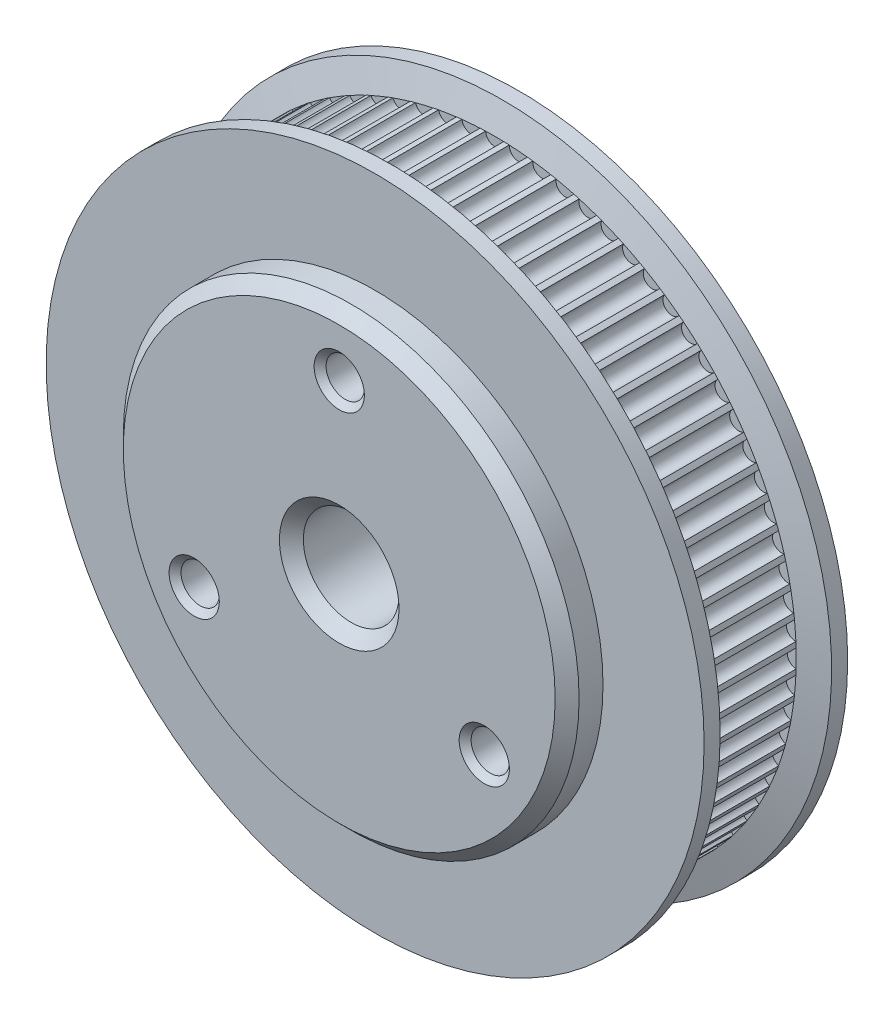
SolidWorks part; units mm, degrees
material "ABS"
ref_plane "Plan de face" through (0, 0, 0) normal (0, 0, 1) x (1, 0, 0)
ref_plane "Plan de dessus" through (0, 0, 0) normal (0, 1, 0) x (1, 0, 0)
ref_plane "Plan de droite" through (0, 0, 0) normal (1, 0, 0) x (0, 0, -1)
sketch "Esquisse1" plane through (0, 0, 0) normal (0, 0, 1) x (1, 0, 0)
  line L0 (0, 0) -> (0, 25.2095) construction
  arc A0 (0.7599, -25.198) -> (1.2194, -25.18) centre (0, 0) ccw
  arc A1 (-0.7599, 25.198) -> (0.7599, 25.198) centre (0, 25.2095) ccw
  arc A2 (-6.6213, 24.3244) -> (-7.0639, 24.1996) centre (0, 0) ccw
  arc A3 (1.2194, 25.18) -> (2.7346, 25.0607) centre (1.9779, 25.1318) ccw
  arc A4 (3.1913, 25.0067) -> (4.6924, 24.7689) centre (3.9436, 24.8991) ccw
  arc A5 (5.1434, 24.6792) -> (6.6213, 24.3244) centre (5.885, 24.513) ccw
  arc A6 (7.0639, 24.1996) -> (8.5093, 23.7299) centre (7.7902, 23.9757) ccw
  arc A7 (8.9408, 23.5708) -> (10.3449, 22.9892) centre (9.6473, 23.2905) ccw
  arc A8 (10.7626, 22.7966) -> (12.1168, 22.1066) centre (11.4449, 22.4618) ccw
  arc A9 (12.518, 21.8819) -> (13.8139, 21.0878) centre (13.1719, 21.4946) ccw
  arc A10 (14.1963, 20.8323) -> (15.4258, 19.939) centre (14.8178, 20.3949) ccw
  arc A11 (15.787, 19.6543) -> (16.9427, 18.6672) centre (16.3723, 19.1695) ccw
  arc A12 (17.2804, 18.355) -> (18.355, 17.2804) centre (17.8258, 17.8258) ccw
  arc A13 (18.6672, 16.9427) -> (19.6543, 15.787) centre (19.1695, 16.3723) ccw
  arc A14 (19.939, 15.4258) -> (20.8323, 14.1963) centre (20.3949, 14.8178) ccw
  arc A15 (21.0878, 13.8139) -> (21.8819, 12.518) centre (21.4946, 13.1719) ccw
  arc A16 (22.1066, 12.1168) -> (22.7966, 10.7626) centre (22.4618, 11.4449) ccw
  arc A17 (22.9892, 10.3449) -> (23.5708, 8.9408) centre (23.2905, 9.6473) ccw
  arc A18 (23.7299, 8.5093) -> (24.1996, 7.0639) centre (23.9757, 7.7902) ccw
  arc A19 (24.3244, 6.6213) -> (24.6792, 5.1434) centre (24.513, 5.885) ccw
  arc A20 (24.7689, 4.6924) -> (25.0067, 3.1913) centre (24.8991, 3.9436) ccw
  arc A21 (25.0607, 2.7346) -> (25.18, 1.2194) centre (25.1318, 1.9779) ccw
  arc A22 (25.198, 0.7599) -> (25.198, -0.7599) centre (25.2095, 0) ccw
  arc A23 (25.18, -1.2194) -> (25.0607, -2.7346) centre (25.1318, -1.9779) ccw
  arc A24 (25.0067, -3.1913) -> (24.7689, -4.6924) centre (24.8991, -3.9436) ccw
  arc A25 (24.6792, -5.1434) -> (24.3244, -6.6213) centre (24.513, -5.885) ccw
  arc A26 (24.1996, -7.0639) -> (23.7299, -8.5093) centre (23.9757, -7.7902) ccw
  arc A27 (23.5708, -8.9408) -> (22.9892, -10.3449) centre (23.2905, -9.6473) ccw
  arc A28 (22.7966, -10.7626) -> (22.1066, -12.1168) centre (22.4618, -11.4449) ccw
  arc A29 (21.8819, -12.518) -> (21.0878, -13.8139) centre (21.4946, -13.1719) ccw
  arc A30 (20.8323, -14.1963) -> (19.939, -15.4258) centre (20.3949, -14.8178) ccw
  arc A31 (19.6543, -15.787) -> (18.6672, -16.9427) centre (19.1695, -16.3723) ccw
  arc A32 (18.355, -17.2804) -> (17.2804, -18.355) centre (17.8258, -17.8258) ccw
  arc A33 (16.9427, -18.6672) -> (15.787, -19.6543) centre (16.3723, -19.1695) ccw
  arc A34 (15.4258, -19.939) -> (14.1963, -20.8323) centre (14.8178, -20.3949) ccw
  arc A35 (13.8139, -21.0878) -> (12.518, -21.8819) centre (13.1719, -21.4946) ccw
  arc A36 (12.1168, -22.1066) -> (10.7626, -22.7966) centre (11.4449, -22.4618) ccw
  arc A37 (10.3449, -22.9892) -> (8.9408, -23.5708) centre (9.6473, -23.2905) ccw
  arc A38 (8.5093, -23.7299) -> (7.0639, -24.1996) centre (7.7902, -23.9757) ccw
  arc A39 (6.6213, -24.3244) -> (5.1434, -24.6792) centre (5.885, -24.513) ccw
  arc A40 (4.6924, -24.7689) -> (3.1913, -25.0067) centre (3.9436, -24.8991) ccw
  arc A41 (2.7346, -25.0607) -> (1.2194, -25.18) centre (1.9779, -25.1318) ccw
  arc A42 (0.7599, -25.198) -> (-0.7599, -25.198) centre (0, -25.2095) ccw
  arc A43 (-1.2194, -25.18) -> (-2.7346, -25.0607) centre (-1.9779, -25.1318) ccw
  arc A44 (-3.1913, -25.0067) -> (-4.6924, -24.7689) centre (-3.9436, -24.8991) ccw
  arc A45 (-5.1434, -24.6792) -> (-6.6213, -24.3244) centre (-5.885, -24.513) ccw
  arc A46 (-7.0639, -24.1996) -> (-8.5093, -23.7299) centre (-7.7902, -23.9757) ccw
  arc A47 (-8.9408, -23.5708) -> (-10.3449, -22.9892) centre (-9.6473, -23.2905) ccw
  arc A48 (-10.7626, -22.7966) -> (-12.1168, -22.1066) centre (-11.4449, -22.4618) ccw
  arc A49 (-12.518, -21.8819) -> (-13.8139, -21.0878) centre (-13.1719, -21.4946) ccw
  arc A50 (-14.1963, -20.8323) -> (-15.4258, -19.939) centre (-14.8178, -20.3949) ccw
  arc A51 (-15.787, -19.6543) -> (-16.9427, -18.6672) centre (-16.3723, -19.1695) ccw
  arc A52 (-17.2804, -18.355) -> (-18.355, -17.2804) centre (-17.8258, -17.8258) ccw
  arc A53 (-18.6672, -16.9427) -> (-19.6543, -15.787) centre (-19.1695, -16.3723) ccw
  arc A54 (-19.939, -15.4258) -> (-20.8323, -14.1963) centre (-20.3949, -14.8178) ccw
  arc A55 (-21.0878, -13.8139) -> (-21.8819, -12.518) centre (-21.4946, -13.1719) ccw
  arc A56 (-22.1066, -12.1168) -> (-22.7966, -10.7626) centre (-22.4618, -11.4449) ccw
  arc A57 (-22.9892, -10.3449) -> (-23.5708, -8.9408) centre (-23.2905, -9.6473) ccw
  arc A58 (-23.7299, -8.5093) -> (-24.1996, -7.0639) centre (-23.9757, -7.7902) ccw
  arc A59 (-24.3244, -6.6213) -> (-24.6792, -5.1434) centre (-24.513, -5.885) ccw
  arc A60 (-24.7689, -4.6924) -> (-25.0067, -3.1913) centre (-24.8991, -3.9436) ccw
  arc A61 (-25.0607, -2.7346) -> (-25.18, -1.2194) centre (-25.1318, -1.9779) ccw
  arc A62 (-25.198, -0.7599) -> (-25.198, 0.7599) centre (-25.2095, 0) ccw
  arc A63 (-25.18, 1.2194) -> (-25.0607, 2.7346) centre (-25.1318, 1.9779) ccw
  arc A64 (-25.0067, 3.1913) -> (-24.7689, 4.6924) centre (-24.8991, 3.9436) ccw
  arc A65 (-24.6792, 5.1434) -> (-24.3244, 6.6213) centre (-24.513, 5.885) ccw
  arc A66 (-24.1996, 7.0639) -> (-23.7299, 8.5093) centre (-23.9757, 7.7902) ccw
  arc A67 (-23.5708, 8.9408) -> (-22.9892, 10.3449) centre (-23.2905, 9.6473) ccw
  arc A68 (-22.7966, 10.7626) -> (-22.1066, 12.1168) centre (-22.4618, 11.4449) ccw
  arc A69 (-21.8819, 12.518) -> (-21.0878, 13.8139) centre (-21.4946, 13.1719) ccw
  arc A70 (-20.8323, 14.1963) -> (-19.939, 15.4258) centre (-20.3949, 14.8178) ccw
  arc A71 (-19.6543, 15.787) -> (-18.6672, 16.9427) centre (-19.1695, 16.3723) ccw
  arc A72 (-18.355, 17.2804) -> (-17.2804, 18.355) centre (-17.8258, 17.8258) ccw
  arc A73 (-16.9427, 18.6672) -> (-15.787, 19.6543) centre (-16.3723, 19.1695) ccw
  arc A74 (-15.4258, 19.939) -> (-14.1963, 20.8323) centre (-14.8178, 20.3949) ccw
  arc A75 (-13.8139, 21.0878) -> (-12.518, 21.8819) centre (-13.1719, 21.4946) ccw
  arc A76 (-12.1168, 22.1066) -> (-10.7626, 22.7966) centre (-11.4449, 22.4618) ccw
  arc A77 (-10.3449, 22.9892) -> (-8.9408, 23.5708) centre (-9.6473, 23.2905) ccw
  arc A78 (-8.5093, 23.7299) -> (-7.0639, 24.1996) centre (-7.7902, 23.9757) ccw
  arc A79 (-6.6213, 24.3244) -> (-5.1434, 24.6792) centre (-5.885, 24.513) ccw
  arc A80 (-4.6924, 24.7689) -> (-3.1913, 25.0067) centre (-3.9436, 24.8991) ccw
  arc A81 (-2.7346, 25.0607) -> (-1.2194, 25.18) centre (-1.9779, 25.1318) ccw
  arc A82 (-8.5093, 23.7299) -> (-8.9408, 23.5708) centre (0, 0) ccw
  arc A83 (-10.3449, 22.9892) -> (-10.7626, 22.7966) centre (0, 0) ccw
  arc A84 (-12.1168, 22.1066) -> (-12.518, 21.8819) centre (0, 0) ccw
  arc A85 (-4.6924, 24.7689) -> (-5.1434, 24.6792) centre (0, 0) ccw
  arc A86 (-2.7346, 25.0607) -> (-3.1913, 25.0067) centre (0, 0) ccw
  arc A87 (-0.7599, 25.198) -> (-1.2194, 25.18) centre (0, 0) ccw
  arc A88 (-13.8139, 21.0878) -> (-14.1963, 20.8323) centre (0, 0) ccw
  arc A89 (-15.4258, 19.939) -> (-15.787, 19.6543) centre (0, 0) ccw
  arc A90 (-16.9427, 18.6672) -> (-17.2804, 18.355) centre (0, 0) ccw
  arc A91 (-18.355, 17.2804) -> (-18.6672, 16.9427) centre (0, 0) ccw
  arc A92 (-19.6543, 15.787) -> (-19.939, 15.4258) centre (0, 0) ccw
  arc A93 (-20.8323, 14.1963) -> (-21.0878, 13.8139) centre (0, 0) ccw
  arc A94 (-21.8819, 12.518) -> (-22.1066, 12.1168) centre (0, 0) ccw
  arc A95 (-22.7966, 10.7626) -> (-22.9892, 10.3449) centre (0, 0) ccw
  arc A96 (-23.5708, 8.9408) -> (-23.7299, 8.5093) centre (0, 0) ccw
  arc A97 (-24.1996, 7.0639) -> (-24.3244, 6.6213) centre (0, 0) ccw
  arc A98 (-24.6792, 5.1434) -> (-24.7689, 4.6924) centre (0, 0) ccw
  arc A99 (-25.0067, 3.1913) -> (-25.0607, 2.7346) centre (0, 0) ccw
  arc A100 (-25.18, 1.2194) -> (-25.198, 0.7599) centre (0, 0) ccw
  arc A101 (-25.198, -0.7599) -> (-25.18, -1.2194) centre (0, 0) ccw
  arc A102 (-25.0607, -2.7346) -> (-25.0067, -3.1913) centre (0, 0) ccw
  arc A103 (-24.7689, -4.6924) -> (-24.6792, -5.1434) centre (0, 0) ccw
  arc A104 (-24.3244, -6.6213) -> (-24.1996, -7.0639) centre (0, 0) ccw
  arc A105 (-23.7299, -8.5093) -> (-23.5708, -8.9408) centre (0, 0) ccw
  arc A106 (-22.9892, -10.3449) -> (-22.7966, -10.7626) centre (0, 0) ccw
  arc A107 (-22.1066, -12.1168) -> (-21.8819, -12.518) centre (0, 0) ccw
  arc A108 (-21.0878, -13.8139) -> (-20.8323, -14.1963) centre (0, 0) ccw
  arc A109 (-19.939, -15.4258) -> (-19.6543, -15.787) centre (0, 0) ccw
  arc A110 (-18.6672, -16.9427) -> (-18.355, -17.2804) centre (0, 0) ccw
  arc A111 (-17.2804, -18.355) -> (-16.9427, -18.6672) centre (0, 0) ccw
  arc A112 (-15.787, -19.6543) -> (-15.4258, -19.939) centre (0, 0) ccw
  arc A113 (-14.1963, -20.8323) -> (-13.8139, -21.0878) centre (0, 0) ccw
  arc A114 (-12.518, -21.8819) -> (-12.1168, -22.1066) centre (0, 0) ccw
  arc A115 (-10.7626, -22.7966) -> (-10.3449, -22.9892) centre (0, 0) ccw
  arc A116 (-8.9408, -23.5708) -> (-8.5093, -23.7299) centre (0, 0) ccw
  arc A117 (-7.0639, -24.1996) -> (-6.6213, -24.3244) centre (0, 0) ccw
  arc A118 (-5.1434, -24.6792) -> (-4.6924, -24.7689) centre (0, 0) ccw
  arc A119 (-3.1913, -25.0067) -> (-2.7346, -25.0607) centre (0, 0) ccw
  arc A120 (-1.2194, -25.18) -> (-0.7599, -25.198) centre (0, 0) ccw
  arc A121 (2.7346, -25.0607) -> (3.1913, -25.0067) centre (0, 0) ccw
  arc A122 (4.6924, -24.7689) -> (5.1434, -24.6792) centre (0, 0) ccw
  arc A123 (6.6213, -24.3244) -> (7.0639, -24.1996) centre (0, 0) ccw
  arc A124 (8.5093, -23.7299) -> (8.9408, -23.5708) centre (0, 0) ccw
  arc A125 (10.3449, -22.9892) -> (10.7626, -22.7966) centre (0, 0) ccw
  arc A126 (12.1168, -22.1066) -> (12.518, -21.8819) centre (0, 0) ccw
  arc A127 (13.8139, -21.0878) -> (14.1963, -20.8323) centre (0, 0) ccw
  arc A128 (15.4258, -19.939) -> (15.787, -19.6543) centre (0, 0) ccw
  arc A129 (16.9427, -18.6672) -> (17.2804, -18.355) centre (0, 0) ccw
  arc A130 (18.355, -17.2804) -> (18.6672, -16.9427) centre (0, 0) ccw
  arc A131 (19.6543, -15.787) -> (19.939, -15.4258) centre (0, 0) ccw
  arc A132 (20.8323, -14.1963) -> (21.0878, -13.8139) centre (0, 0) ccw
  arc A133 (21.8819, -12.518) -> (22.1066, -12.1168) centre (0, 0) ccw
  arc A134 (22.7966, -10.7626) -> (22.9892, -10.3449) centre (0, 0) ccw
  arc A135 (23.5708, -8.9408) -> (23.7299, -8.5093) centre (0, 0) ccw
  arc A136 (24.1996, -7.0639) -> (24.3244, -6.6213) centre (0, 0) ccw
  arc A137 (24.6792, -5.1434) -> (24.7689, -4.6924) centre (0, 0) ccw
  arc A138 (25.0067, -3.1913) -> (25.0607, -2.7346) centre (0, 0) ccw
  arc A139 (25.18, -1.2194) -> (25.198, -0.7599) centre (0, 0) ccw
  arc A140 (25.198, 0.7599) -> (25.18, 1.2194) centre (0, 0) ccw
  arc A141 (25.0607, 2.7346) -> (25.0067, 3.1913) centre (0, 0) ccw
  arc A142 (24.7689, 4.6924) -> (24.6792, 5.1434) centre (0, 0) ccw
  arc A143 (24.3244, 6.6213) -> (24.1996, 7.0639) centre (0, 0) ccw
  arc A144 (23.7299, 8.5093) -> (23.5708, 8.9408) centre (0, 0) ccw
  arc A145 (22.9892, 10.3449) -> (22.7966, 10.7626) centre (0, 0) ccw
  arc A146 (22.1066, 12.1168) -> (21.8819, 12.518) centre (0, 0) ccw
  arc A147 (21.0878, 13.8139) -> (20.8323, 14.1963) centre (0, 0) ccw
  arc A148 (19.939, 15.4258) -> (19.6543, 15.787) centre (0, 0) ccw
  arc A149 (1.2194, 25.18) -> (0.7599, 25.198) centre (0, 0) ccw
  arc A150 (3.1913, 25.0067) -> (2.7346, 25.0607) centre (0, 0) ccw
  arc A151 (5.1434, 24.6792) -> (4.6924, 24.7689) centre (0, 0) ccw
  arc A152 (7.0639, 24.1996) -> (6.6213, 24.3244) centre (0, 0) ccw
  arc A153 (8.9408, 23.5708) -> (8.5093, 23.7299) centre (0, 0) ccw
  arc A154 (10.7626, 22.7966) -> (10.3449, 22.9892) centre (0, 0) ccw
  arc A155 (12.518, 21.8819) -> (12.1168, 22.1066) centre (0, 0) ccw
  arc A156 (14.1963, 20.8323) -> (13.8139, 21.0878) centre (0, 0) ccw
  arc A157 (15.787, 19.6543) -> (15.4258, 19.939) centre (0, 0) ccw
  arc A158 (17.2804, 18.355) -> (16.9427, 18.6672) centre (0, 0) ccw
  arc A159 (18.6672, 16.9427) -> (18.355, 17.2804) centre (0, 0) ccw
  point P166 (0, 0)
  dimension "D1" = 50.419
  dimension "D3" = 0.7599
  dimension "D2" = 80
extrude "Boss.-Extru.1" add sketch "Esquisse1" along normal blind 6 and the other way blind 6
sketch "Esquisse3" plane through (0, 0, 6) normal (0, 0, 1) x (1, 0, 0)
  circle A0 centre (0, 0) radius 27.5
  dimension "D1" = 55
extrude "Boss.-Extru.2" add sketch "Esquisse3" against normal blind 2
sketch "Esquisse4" plane through (0, 0, 0) normal (1, 0, 0) x (0, 0, -1)
  line L0 (-4, 25.198) -> (-5.3511, 29.9099)
  line L1 (-4, -27.5) -> (-4, 27.5) construction
  line L2 (-5.3511, 29.9099) -> (-1.4485, 29.9099)
  line L3 (-1.4485, 29.9099) -> (-4, 25.198)
  line L5 (6, 25.198) -> (-4, 25.198) construction
  line L6 (-9.4472, 0) -> (9.0572, 0) construction
  dimension "D1" = 16
revolve "Enlèvement de matière-Révolution1" cut sketch "Esquisse4" angle 360 about L6
mirror "Symétrie1" about plane through (0, 0, 0) normal (0, 0, 1) of "Enlèvement de matière-Révolution1", "Boss.-Extru.2"
sketch "Esquisse6" plane through (0, 0, 0) normal (0, 0, 1) x (1, 0, 0)
  line L0 (0, -30.8325) -> (0, 29.9617) construction
  line L1 (-32.1386, 0) -> (30.5554, 0) construction
  circle A0 centre (0, 0) radius 4
  circle A1 centre (0, 14) radius 1.6
  circle A2 centre (12.1244, -7) radius 1.6
  circle A3 centre (-12.1244, -7) radius 1.6
  point P16 (0, 0)
  dimension "D1" = 8
  dimension "D2" = 3.2
  dimension "D3" = 14
  dimension "D4" = 3
sketch "Esquisse7" plane through (0, 0, 6) normal (0, 0, 1) x (1, 0, 0)
  circle A0 centre (0, 0) radius 19.05
  dimension "D1" = 38.1
extrude "Boss.-Extru.3" add sketch "Esquisse7" along normal blind 3
extrude "Enlèv. mat.-Extru.1" cut sketch "Esquisse6" against normal through all and the other way through all
chamfer "Chanfrein4" distance 1 angle 45 3 edges at (4, 0, 9) (4, 0, -6) (19.05, 0, 9)
chamfer "Chanfrein5" distance 0.5 angle 45 6 edges at (-10.5244, -7, -6) (13.7244, -7, -6) (1.6, 14, -6) (-10.5244, -7, 9) (1.6, 14, 9) (13.7244, -7, 9)
equation "\"p\"= 2'Pitch (p)"
equation "\"Da\"= 50.419'Outside Diameter (Da)"
equation "\"h\"= 0.76'Grooves Depths (h)"
equation "\"Df\"= \"Da\" - ( 2 * \"h\" )'Root Diameter (Dp)"
equation "\"Z\"= 80'Number of Teeths (Z)"
equation "\"D1@Esquisse1\"= \"Da\""
